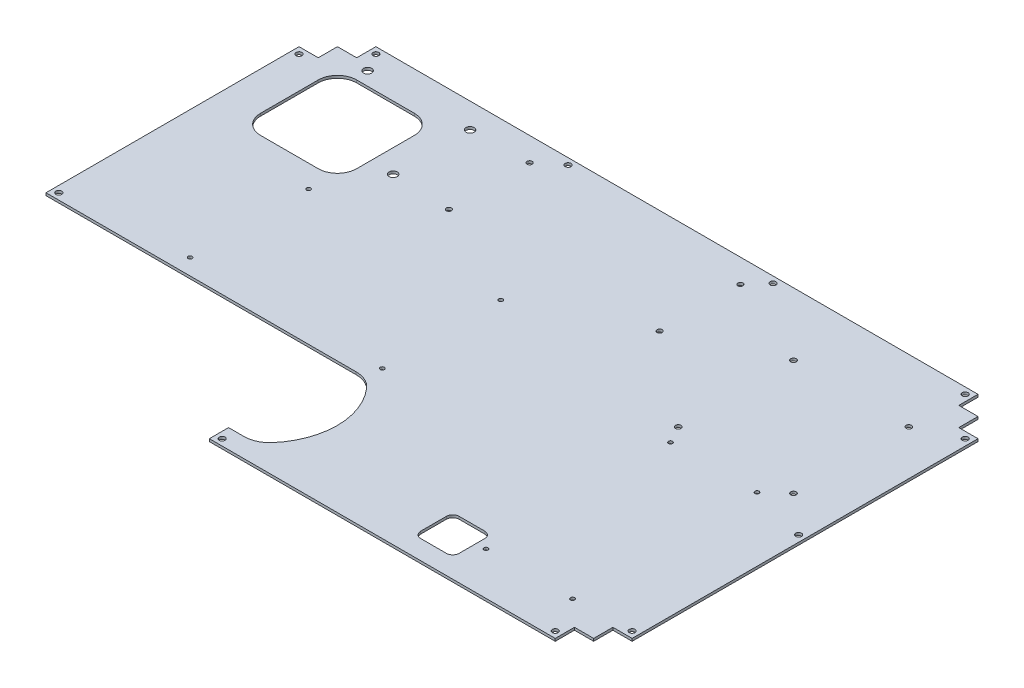
SolidWorks part; units mm, degrees
ref_plane "Front Plane" through (0, 0, 0) normal (0, 0, 1) x (1, 0, 0)
ref_plane "Top Plane" through (0, 0, 0) normal (0, 1, 0) x (1, 0, 0)
ref_plane "Right Plane" through (0, 0, 0) normal (1, 0, 0) x (0, 0, -1)
sketch "Sketch1" plane through (0, 0, 0) normal (0, 1, 0) x (1, 0, 0)
  line L0 (-250, -150) -> (-235, -150)
  line L1 (-250, -150) -> (250, -150) construction
  line L2 (-250, -150) -> (-250, 150) construction
  line L3 (-250, 150) -> (250, 150) construction
  line L4 (250, -150) -> (250, 150) construction
  line L5 (-250, -150) -> (250, 150) construction
  line L6 (-250, 150) -> (250, -150) construction
  line L7 (-235, -150) -> (-235, -165)
  line L8 (-235, -165) -> (235, -165)
  line L9 (235, -165) -> (235, -150)
  line L10 (235, -150) -> (250, -150)
  line L11 (250, -150) -> (250, -135)
  line L12 (250, -135) -> (265, -135)
  line L13 (265, -135) -> (265, 135)
  line L14 (265, 135) -> (250, 135)
  line L15 (250, 135) -> (250, 150)
  line L16 (250, 150) -> (235, 150)
  line L17 (235, 150) -> (235, 165)
  line L18 (235, 165) -> (-235, 165)
  line L19 (-235, 165) -> (-235, 150)
  line L20 (-235, 150) -> (-250, 150)
  line L21 (-250, 150) -> (-250, 135)
  line L22 (-250, 135) -> (-265, 135)
  line L23 (-265, 135) -> (-265, -135)
  line L24 (-265, -135) -> (-250, -135)
  line L25 (-250, -135) -> (-250, -150)
  point P0 (0, 0)
  dimension "D1" = 500
  dimension "D2" = 300
  dimension "D3" = 15
  dimension "D4" = 15
base flange "Base-Flange1" sketch "Sketch1" thickness 2 reverse thickness direction no parameters "D1"=1
sketch "Sketch2" plane through (0, 0, 0) normal (0, 1, 0) x (1, 0, 0)
  line L0 (-265, 135) -> (-265, -135) construction
  line L1 (-265, -62.5) -> (-22.9093, -62.5)
  line L2 (-265, -62.5) -> (-265, -165)
  line L3 (-265, -165) -> (-15, -165) construction
  line L4 (-15, -62.5) -> (-15, -165) construction
  line L5 (-235, -165) -> (235, -165) construction
  line L6 (-22.9093, -150) -> (-35, -150)
  line L7 (-35, -150) -> (-35, -165)
  line L8 (-35, -165) -> (-265, -165)
  arc A0 (-7.8703, -69.3156) -> (-7.8703, -143.1844) centre (-50, -106.25) cw
  arc A1 (-7.8703, -143.1844) -> (-22.9093, -150) centre (-22.9093, -130) cw
  arc A2 (-22.9093, -62.5) -> (-7.8703, -69.3156) centre (-22.9093, -82.5) cw
  point P15 (-15, -150)
  dimension "D6" = 20
  dimension "D1" = 102.5
  dimension "D2" = 250
  dimension "D3" = 15
  dimension "D4" = 35
  dimension "D5" = 20
extrude "Cut-Extrude1" cut sketch "Sketch2" against normal up to next normal cut yes
sketch "Sketch3" plane through (0, 0, 0) normal (0, 1, 0) x (1, 0, 0)
  line L0 (-235, 135) -> (-235, 150) construction
  line L1 (-220, 135) -> (-175, 135)
  line L2 (-235, 120) -> (-235, 75)
  line L3 (-220, 60) -> (-175, 60)
  line L4 (-160, 120) -> (-160, 75)
  line L5 (-235, 150) -> (-250, 150) construction
  line L6 (-235, 135) -> (-250, 135) construction
  line L7 (-250, 150) -> (-250, 135) construction
  arc A0 (-220, 60) -> (-235, 75) centre (-220, 75) cw
  arc A1 (-175, 60) -> (-160, 75) centre (-175, 75) ccw
  arc A2 (-175, 135) -> (-160, 120) centre (-175, 120) cw
  arc A3 (-220, 135) -> (-235, 120) centre (-220, 120) ccw
  point P13 (-235, 60)
  dimension "D3" = 15
  dimension "D1" = 75
  dimension "D2" = 15
extrude "Cut-Extrude2" cut sketch "Sketch3" against normal up to next normal cut yes
sketch "Sketch4" plane through (0, 0, 0) normal (0, 1, 0) x (1, 0, 0)
  line L0 (265, -135) -> (265, 135) construction
  line L1 (115, -120) -> (135, -120)
  line L2 (110, -125) -> (110, -145)
  line L3 (115, -150) -> (135, -150)
  line L4 (140, -125) -> (140, -145)
  line L5 (-35, -165) -> (235, -165) construction
  arc A0 (110, -145) -> (115, -150) centre (115, -145) ccw
  arc A1 (135, -120) -> (140, -125) centre (135, -125) cw
  arc A2 (135, -150) -> (140, -145) centre (135, -145) ccw
  arc A3 (115, -120) -> (110, -125) centre (115, -125) ccw
  point P10 (110, -150)
  point P15 (140, -150)
  dimension "D4" = 5
  dimension "D1" = 125
  dimension "D2" = 30
  dimension "D3" = 15
extrude "Cut-Extrude3" cut sketch "Sketch4" against normal up to next normal cut yes
hole_wizard "M4 Clearance Hole1" positions "Sketch5" profile "Sketch6" hole size "M4" standard "DIN" end condition up to next
sketch "Sketch5" plane through (0, 0, 0) normal (0, 1, 0) x (1, 0, 0)
  line L0 (-265, 135) -> (-265, -62.5) construction
  line L1 (235, 165) -> (-235, 165) construction
  line L2 (265, -135) -> (265, 135) construction
  line L3 (-35, -165) -> (235, -165) construction
  line L4 (-22.9093, -62.5) -> (-265, -62.5) construction
  line L5 (-250, 135) -> (-265, 135) construction
  line L6 (-235, 165) -> (-235, 150) construction
  line L7 (235, 150) -> (235, 165) construction
  line L8 (265, 135) -> (250, 135) construction
  line L9 (250, -135) -> (265, -135) construction
  line L10 (235, -165) -> (235, -150) construction
  line L11 (-35, -165) -> (-35, -150) construction
  point P0 (-230, 160)
  point P2 (-80, 160)
  point P4 (80, 160)
  point P6 (230, 160)
  point P8 (260, 130)
  point P10 (260, 0)
  point P12 (260, -130)
  point P14 (230, -160)
  point P16 (-30, -160)
  point P18 (-260, 130)
  point P20 (-260, -57.5)
  point P54 (265, 0)
  dimension "D1" = 5
  dimension "D2" = 5
  dimension "D3" = 5
  dimension "D4" = 5
  dimension "D5" = 5
  dimension "D6" = 5
  dimension "D7" = 5
  dimension "D8" = 5
  dimension "D9" = 5
  dimension "D10" = 5
  dimension "D11" = 5
  dimension "D12" = 5
  dimension "D13" = 150
  dimension "D14" = 150
sketch "Sketch6" plane through (-230, 0, -160) normal (1, 0, 0) x (0, 0, 1)
  line L0 (0, 0) -> (0, 2)
  line L1 (0, 2) -> (2.25, 2)
  line L2 (2.25, 2) -> (2.25, 0)
  line L5 (2.25, 0) -> (0, 0)
  line L11 (0, -6.35) -> (0, 107.95) construction
  dimension "Thru Hole Dia." = 4.5
  dimension "Thru Hole Depth" = 2
sketch "Sketch7" plane through (0, 0, 0) normal (0, 1, 0) x (1, 0, 0)
  line L0 (235, 165) -> (-235, 165) construction
  line L1 (-96.5, 146.5) -> (68, 146.5) construction
  line L2 (-96.5, 146.5) -> (-96.5, 83.5) construction
  line L3 (-96.5, 83.5) -> (68, 83.5) construction
  line L4 (68, 146.5) -> (68, 83.5) construction
  line L5 (-96.5, 146.5) -> (68, 83.5) construction
  line L6 (-96.5, 83.5) -> (68, 146.5) construction
  line L7 (-265, 135) -> (-265, -62.5) construction
  circle A0 centre (-96.5, 146.5) radius 2
  circle A1 centre (-96.5, 83.5) radius 2
  circle A2 centre (68, 83.5) radius 2
  circle A3 centre (68, 146.5) radius 2
  point P0 (-14.25, 115)
  dimension "D5" = 4
  dimension "D1" = 164.5
  dimension "D2" = 63
  dimension "D3" = 18.5
  dimension "D4" = 168.5
extrude "Cut-Extrude4" cut sketch "Sketch7" against normal up to next normal cut yes
hole_wizard "M3 Clearance Hole1" positions "Sketch9" profile "Sketch10" hole size "M3" standard "DIN" end condition up to next
sketch "Sketch9" plane through (0, 0, 0) normal (0, 1, 0) x (1, 0, 0)
  line L1 (147.5, 12.5) -> (215, 12.5) construction
  line L2 (147.5, 12.5) -> (147.5, -131.5) construction
  line L3 (147.5, -131.5) -> (215, -131.5) construction
  line L4 (215, 12.5) -> (215, -131.5) construction
  line L5 (265, -135) -> (265, 135) construction
  line L6 (-35, -165) -> (235, -165) construction
  line L8 (-15, -50) -> (-165, -50) construction
  line L9 (-15, -50) -> (-15, 42.5) construction
  line L10 (-15, 42.5) -> (-165, 42.5) construction
  line L11 (-165, -50) -> (-165, 42.5) construction
  line L12 (-265, 135) -> (-265, -62.5) construction
  point P1 (147.5, 12.5)
  point P2 (215, -131.5)
  point P89 (147.5, -131.5)
  point P90 (215, 12.5)
  point P104 (-15, -50)
  point P105 (-165, 42.5)
  point P144 (-15, 42.5)
  point P145 (-165, -50)
  dimension "D1" = 144
  dimension "D2" = 67.5
  dimension "D3" = 50
  dimension "D4" = 33.5
  dimension "D5" = 92.5
  dimension "D6" = 150
  dimension "D7" = 100
  dimension "D8" = 115
sketch "Sketch10" plane through (147.5, 0, -12.5) normal (1, 0, 0) x (0, 0, 1)
  line L0 (0, 0) -> (0, 2)
  line L1 (0, 2) -> (1.6, 2)
  line L2 (1.6, 2) -> (1.6, 0)
  line L5 (1.6, 0) -> (0, 0)
  line L11 (0, -6.35) -> (0, 107.95) construction
  dimension "Thru Hole Dia." = 3.2
  dimension "Thru Hole Depth" = 2
hole_wizard "M6 Clearance Hole1" positions "Sketch13" profile "Sketch14" hole size "M6" standard "DIN" end condition up to next
sketch "Sketch13" plane through (0, 0, 0) normal (0, 1, 0) x (1, 0, 0)
  line L1 (-222, 145.5) -> (-142, 145.5) construction
  line L2 (-222, 145.5) -> (-222, 85.5) construction
  line L3 (-222, 85.5) -> (-142, 85.5) construction
  line L4 (-142, 145.5) -> (-142, 85.5) construction
  line L5 (235, 165) -> (-235, 165) construction
  line L6 (-265, 135) -> (-265, -62.5) construction
  point P0 (-142, 145.5)
  point P2 (-222, 145.5)
  point P4 (-142, 85.5)
  point P52 (-124.1563, 153.2926)
  dimension "D4" = 43
  dimension "D1" = 80
  dimension "D2" = 60
  dimension "D3" = 19.5
sketch "Sketch14" plane through (-142, 0, -145.5) normal (1, 0, 0) x (0, 0, 1)
  line L0 (0, 0) -> (0, 2)
  line L1 (0, 2) -> (3.2, 2)
  line L2 (3.2, 2) -> (3.2, 0)
  line L5 (3.2, 0) -> (0, 0)
  line L11 (0, -6.35) -> (0, 107.95) construction
  dimension "Thru Hole Dia." = 6.4
  dimension "Thru Hole Depth" = 2
hole_wizard "M4 Clearance Hole2" positions "Sketch15" profile "Sketch16" hole size "M4" standard "DIN" end condition up to next
sketch "Sketch15" plane through (0, 0, 0) normal (0, 1, 0) x (1, 0, 0)
  line L1 (230, 116) -> (140, 116) construction
  line L2 (230, 116) -> (230, 26) construction
  line L3 (230, 26) -> (140, 26) construction
  line L4 (140, 116) -> (140, 26) construction
  line L5 (235, 165) -> (-235, 165) construction
  line L6 (265, -135) -> (265, 135) construction
  point P0 (230, 116)
  point P4 (140, 26)
  point P75 (230, 26)
  point P76 (140, 116)
  dimension "D1" = 90
  dimension "D2" = 49
  dimension "D3" = 35
sketch "Sketch16" plane through (230, 0, -116) normal (1, 0, 0) x (0, 0, 1)
  line L0 (0, 0) -> (0, 2)
  line L1 (0, 2) -> (2.15, 2)
  line L2 (2.15, 2) -> (2.15, 0)
  line L5 (2.15, 0) -> (0, 0)
  line L11 (0, -6.35) -> (0, 107.95) construction
  dimension "Thru Hole Dia." = 4.3
  dimension "Thru Hole Depth" = 2
sketch "Bend-Lines1" [suppressed] plane through (0, 0, 0) normal (0, 1, 0) x (1, 0, 0)
sketch "Bounding-Box1" [suppressed] plane through (0, 0, 0) normal (0, 1, 0) x (1, 0, 0)
sheet metal parameters "Sheet-Metal1" thickness 2 parameters "D1"=1
flat pattern "Flat-Pattern1" [suppressed]
sketch "Bend-Lines2" plane through (0, 0, 0) normal (0, 1, 0) x (1, 0, 0)
sketch3d "Bounding-Box2" [suppressed]
  line L0 (265, 165, 0) -> (-265, 165, 0) construction
  line L1 (265, -165, 0) -> (-265, -165, 0) construction
  line L2 (265, 165, 0) -> (265, -165, 0) construction
  line L3 (-265, 165, 0) -> (-265, -165, 0) construction
sheet metal parameters "Sheet-Metal3" thickness 2 parameters "D1"=1
flat pattern "Flat-Pattern1"
sketch "Bend-Lines2" plane through (0, 0, 0) normal (0, 1, 0) x (1, 0, 0)
sketch3d "Bounding-Box2" [suppressed]
  line L0 (265, 165, 0) -> (-265, 165, 0) construction
  line L1 (265, -165, 0) -> (-265, -165, 0) construction
  line L2 (265, 165, 0) -> (265, -165, 0) construction
  line L3 (-265, 165, 0) -> (-265, -165, 0) construction
sheet metal parameters "Sheet-Metal5" thickness 2 parameters "D1"=1
flat pattern "Flat-Pattern1"
sketch "Bend-Lines2" plane through (0, 0, 0) normal (0, 1, 0) x (1, 0, 0)
sketch3d "Bounding-Box2" [suppressed]
  line L0 (265, 165, 0) -> (-265, 165, 0) construction
  line L1 (265, -165, 0) -> (-265, -165, 0) construction
  line L2 (265, 165, 0) -> (265, -165, 0) construction
  line L3 (-265, 165, 0) -> (-265, -165, 0) construction
sheet metal parameters "Sheet-Metal6" thickness 2 parameters "D1"=1
flat pattern "Flat-Pattern1"
sketch "Bend-Lines2" plane through (0, 0, 0) normal (0, 1, 0) x (1, 0, 0)
sketch3d "Bounding-Box2" [suppressed]
  line L0 (265, 165, 0) -> (-265, 165, 0) construction
  line L1 (265, -165, 0) -> (-265, -165, 0) construction
  line L2 (265, 165, 0) -> (265, -165, 0) construction
  line L3 (-265, 165, 0) -> (-265, -165, 0) construction
sheet metal parameters "Sheet-Metal7" thickness 2 parameters "D1"=1
flat pattern "Flat-Pattern1"
sketch "Bend-Lines2" plane through (0, 0, 0) normal (0, 1, 0) x (1, 0, 0)
sketch3d "Bounding-Box2" [suppressed]
  line L0 (265, 165, 0) -> (-265, 165, 0) construction
  line L1 (265, -165, 0) -> (-265, -165, 0) construction
  line L2 (265, 165, 0) -> (265, -165, 0) construction
  line L3 (-265, 165, 0) -> (-265, -165, 0) construction
sheet metal parameters "Sheet-Metal8" thickness 2 parameters "D1"=1
flat pattern "Flat-Pattern1"
sketch "Bend-Lines2" plane through (0, 0, 0) normal (0, 1, 0) x (1, 0, 0)
sketch3d "Bounding-Box2" [suppressed]
  line L0 (265, 165, 0) -> (-265, 165, 0) construction
  line L1 (265, -165, 0) -> (-265, -165, 0) construction
  line L2 (265, 165, 0) -> (265, -165, 0) construction
  line L3 (-265, 165, 0) -> (-265, -165, 0) construction
sheet metal parameters "Sheet-Metal9" thickness 2 parameters "D1"=1
flat pattern "Flat-Pattern1"
sketch "Bend-Lines2" plane through (0, 0, 0) normal (0, 1, 0) x (1, 0, 0)
sketch3d "Bounding-Box2" [suppressed]
  line L0 (265, 165, 0) -> (-265, 165, 0) construction
  line L1 (265, -165, 0) -> (-265, -165, 0) construction
  line L2 (265, 165, 0) -> (265, -165, 0) construction
  line L3 (-265, 165, 0) -> (-265, -165, 0) construction
sheet metal parameters "Sheet-Metal10" thickness 2 parameters "D1"=1
flat pattern "Flat-Pattern1"
sketch "Bend-Lines2" plane through (0, 0, 0) normal (0, 1, 0) x (1, 0, 0)
sketch3d "Bounding-Box2" [suppressed]
  line L0 (265, 165, 0) -> (-265, 165, 0) construction
  line L1 (265, -165, 0) -> (-265, -165, 0) construction
  line L2 (265, 165, 0) -> (265, -165, 0) construction
  line L3 (-265, 165, 0) -> (-265, -165, 0) construction
sheet metal parameters "Sheet-Metal11" thickness 2 parameters "D1"=1
flat pattern "Flat-Pattern1"
sketch "Bend-Lines2" plane through (0, 0, 0) normal (0, 1, 0) x (1, 0, 0)
sketch3d "Bounding-Box2" [suppressed]
  line L0 (265, 165, 0) -> (-265, 165, 0) construction
  line L1 (265, -165, 0) -> (-265, -165, 0) construction
  line L2 (265, 165, 0) -> (265, -165, 0) construction
  line L3 (-265, 165, 0) -> (-265, -165, 0) construction
